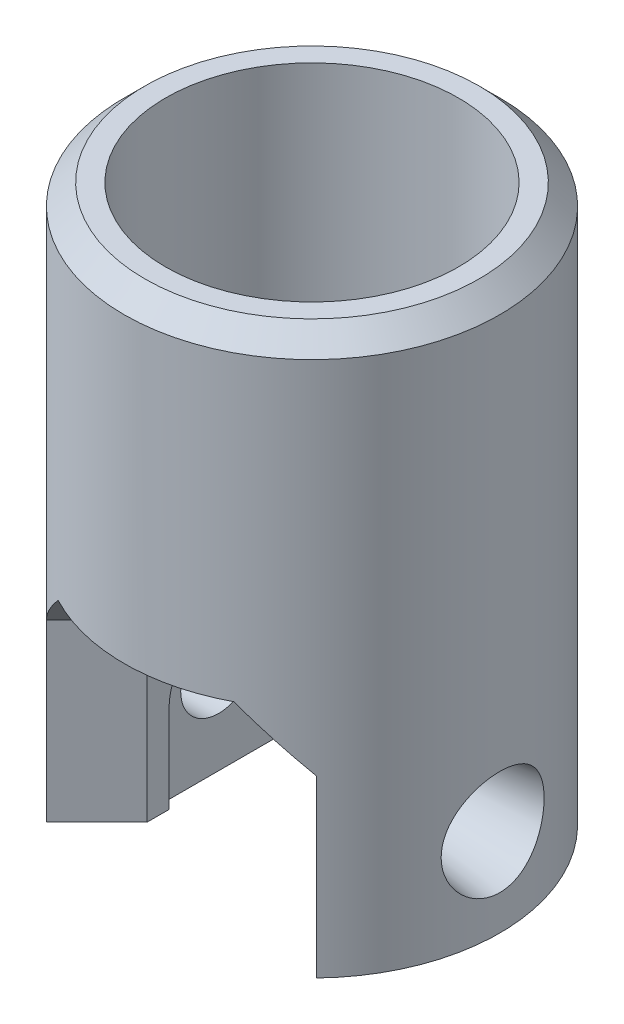
SolidWorks part; units mm, degrees
material "6061-T6 (SS)"
ref_plane "Front Plane" through (0, 0, 0) normal (0, 0, 1) x (1, 0, 0)
ref_plane "Top Plane" through (0, 0, 0) normal (0, 1, 0) x (1, 0, 0)
ref_plane "Right Plane" through (0, 0, 0) normal (1, 0, 0) x (0, 0, -1)
sketch "Sketch1" plane through (0, 0, 0) normal (0, 1, 0) x (1, 0, 0)
  circle A0 centre (0, 0) radius 5.6388 construction
  circle A1 centre (0, 0) radius 6.35 construction
  circle A2 centre (0, 0) radius 6.3754
  circle A3 centre (0, 0) radius 5.588
  circle A4 centre (0, 0) radius 8.1754
  dimension "D1" = 12.7
  dimension "D2" = 11.2776
  dimension "D3" = 0.0254
  dimension "D4" = 0.0508
  dimension "D5" = 1.8
extrude "Boss-Extrude1" add sketch "Sketch1" along normal blind 12.7 contours A4 A2 | A3 region at (0, 0, 0) region at (-7.9442, 0, 0)
sketch "Sketch2" plane through (0, 0, 0) normal (0, -1, 0) x (1, 0, 0)
  circle A1 centre (0, 0) radius 8.1754
  circle A2 centre (0, 0) radius 8.1754
  dimension "D1" = 0
extrude "Boss-Extrude2" add sketch "Sketch2" along normal blind 1.35
sketch "Sketch3" plane through (0, -1.35, 0) normal (0, -1, 0) x (1, 0, 0)
  line L0 (3.683, -3.4925) -> (3.683, 3.4925)
  line L1 (0, 0) -> (0, 8.1754) construction
  line L2 (3.683, 3.4925) -> (5.8753, 5.6848)
  line L3 (3.683, -3.4925) -> (5.8753, -5.6848)
  line L4 (0, 0) -> (3.683, 0) construction
  line L5 (-3.683, -3.4925) -> (-5.8753, -5.6848)
  line L6 (-3.683, 3.4925) -> (-5.8753, 5.6848)
  line L7 (-3.683, -3.4925) -> (-3.683, 3.4925)
  circle A0 centre (0, 0) radius 8.1754 construction
  arc A1 (5.8753, 5.6848) -> (5.8753, -5.6848) centre (0, 0) cw
  arc A2 (5.8753, 5.6848) -> (5.8753, -5.6848) centre (0, 0) cw
  arc A3 (-5.8753, 5.6848) -> (-5.8753, -5.6848) centre (0, 0) ccw
  arc A4 (-5.8753, 5.6848) -> (-5.8753, -5.6848) centre (0, 0) ccw
  point P11 (3.683, 0)
  circle M3 centre (0, 0) radius 8.1754
  dimension "D1" = 3.683
  dimension "D2" = 6.985
extrude "Boss-Extrude3" add sketch "Sketch3" along normal blind 10.16 contours L0 L3 L2 M3 | L5 L7 L6 M3 region at (5.7828, -1.35, 0) region at (-5.7828, -1.35, 0)
chamfer "Chamfer1" distance 2.54 angle 45 6 edges at (-4.7792, -1.35, -4.5887) (-4.7792, -1.35, 4.5887) (-3.683, -1.35, 0) (4.7792, -1.35, -4.5887) (4.7792, -1.35, 4.5887) (3.683, -1.35, 0)
ref_plane "Plane1" through (-8.1754, 0, 0) normal (-1, 0, 0) x (0, 0, 1)
sketch "Sketch4" plane through (-8.1754, 0, 0) normal (-1, 0, 0) x (0, 0, 1)
  line L1 (-5.6848, -11.51) -> (5.6848, -11.51) construction
  circle A0 centre (0, -7.7) radius 2.54 construction
  circle A1 centre (0, -7.7) radius 1.651
  circle A2 centre (0, -7.7) radius 2.2844
  dimension "D1" = 5.08
  dimension "D3" = 3.302
  dimension "D4" = 4.5688
  dimension "D2" = 3.81
ref_plane "Plane2" through (8.1754, 0, 0) normal (1, 0, 0) x (0, 0, -1)
extrude "Cut-Extrude2" cut sketch "Sketch4<3>" along normal blind 3.683 draft 8 from surface contours A2 A1 | A1 region at (-8.1754, -7.7, 0) region at (-8.1754, -7.7, -2.2198) starting at plane "Plane2"
sketch "Sketch4<3>" plane through (-8.1754, 0, 0) normal (-1, 0, 0) x (0, 0, 1) same geometry as "Sketch4"
extrude "Cut-Extrude1" cut sketch "Sketch4" against normal through all contours A1 region at (-8.1754, -7.7, 0)
sketch "Sketch7" plane through (0, 12.7, 0) normal (0, 1, 0) x (1, 0, 0)
  circle A1 centre (0, 0) radius 5.588
  circle A2 centre (0, 0) radius 5.588
  dimension "D1" = 0
extrude "Cut-Extrude4" cut sketch "Sketch7" against normal blind 6.35
sketch "Sketch8" plane through (0, 6.35, 0) normal (0, 1, 0) x (1, 0, 0)
  circle A2 centre (0, 0) radius 4.688
  circle A3 centre (0, 0) radius 4.688
  dimension "D1" = 0.9
extrude "Cut-Extrude5" cut sketch "Sketch8" against normal blind 3.81 draft 45
sketch "Sketch9" plane through (-3.683, 0, 0) normal (1, 0, 0) x (0, 0, -1)
  circle A0 centre (0, -7.7) radius 5.08
  dimension "D1" = 10.16
sketch "Sketch10" plane through (0, 6.35, 0) normal (0, 1, 0) x (1, 0, 0)
  circle A1 centre (0, 0) radius 5.588
  circle A2 centre (0, 0) radius 5.588
  dimension "D1" = 0
extrude "Cut-Extrude7" cut sketch "Sketch10" against normal up to surface (6.35 mm away) up to face at (0, 0, -5.588)
sketch "Sketch12" plane through (-3.683, 0, 0) normal (1, 0, 0) x (0, 0, -1)
  line L0 (2.54, -11.51) -> (2.54, -7.7)
  line L1 (3.4925, -11.51) -> (-3.4925, -11.51) construction
  line L2 (2.54, -11.51) -> (-2.54, -11.51)
  line L3 (-2.54, -11.51) -> (-2.54, -7.7)
  line L4 (0, -7.7) -> (0, -11.51) construction
  arc A0 (-2.54, -7.7) -> (2.54, -7.7) centre (0, -7.7) cw
  dimension "D2" = 2.54
  dimension "D1" = 5.08
extrude "Cut-Extrude8" cut sketch "Sketch12" against normal blind 4.064 and the other way blind 4.064 from surface starting at plane "Right Plane"
chamfer "Chamfer4" distance 0.9 angle 45 1 edges at (0, 12.7, 8.1754)
ref_plane "Plane3" through (0, 0, -8.1754) normal (0, 0, -1) x (-1, 0, 0)
